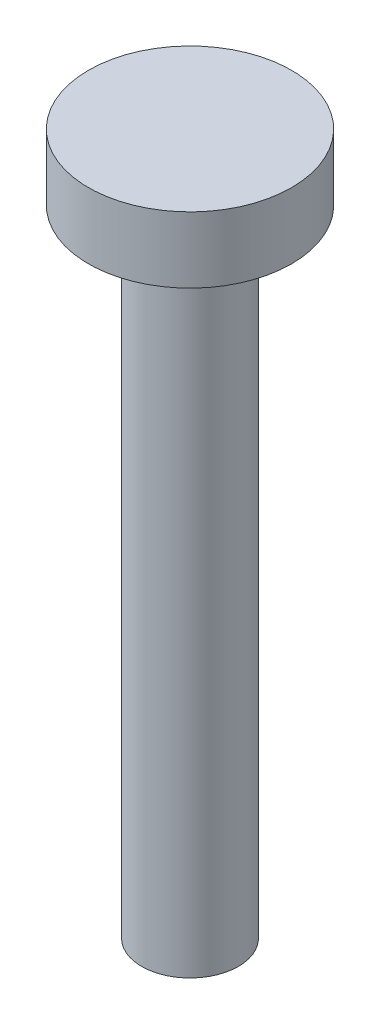
SolidWorks part; units mm, degrees
material "Brass"
ref_plane "Front Plane" through (0, 0, 0) normal (0, 0, 1) x (1, 0, 0)
ref_plane "Top Plane" through (0, 0, 0) normal (0, 1, 0) x (1, 0, 0)
ref_plane "Right Plane" through (0, 0, 0) normal (1, 0, 0) x (0, 0, -1)
sketch "Sketch1" plane through (0, 0, 0) normal (0, 0, 1) x (1, 0, 0)
  line L0 (0, 0) -> (0, 69) construction
  line L1 (0, 0) -> (4.7625, 0)
  line L2 (4.7625, 0) -> (4.7625, 62.5)
  line L3 (4.7625, 62.5) -> (10, 62.5)
  line L4 (10, 62.5) -> (10, 69)
  line L5 (10, 69) -> (0, 69)
  line L6 (0, 69) -> (0, 0)
revolve "Revolve1" add sketch "Sketch1" angle 360 about L0
